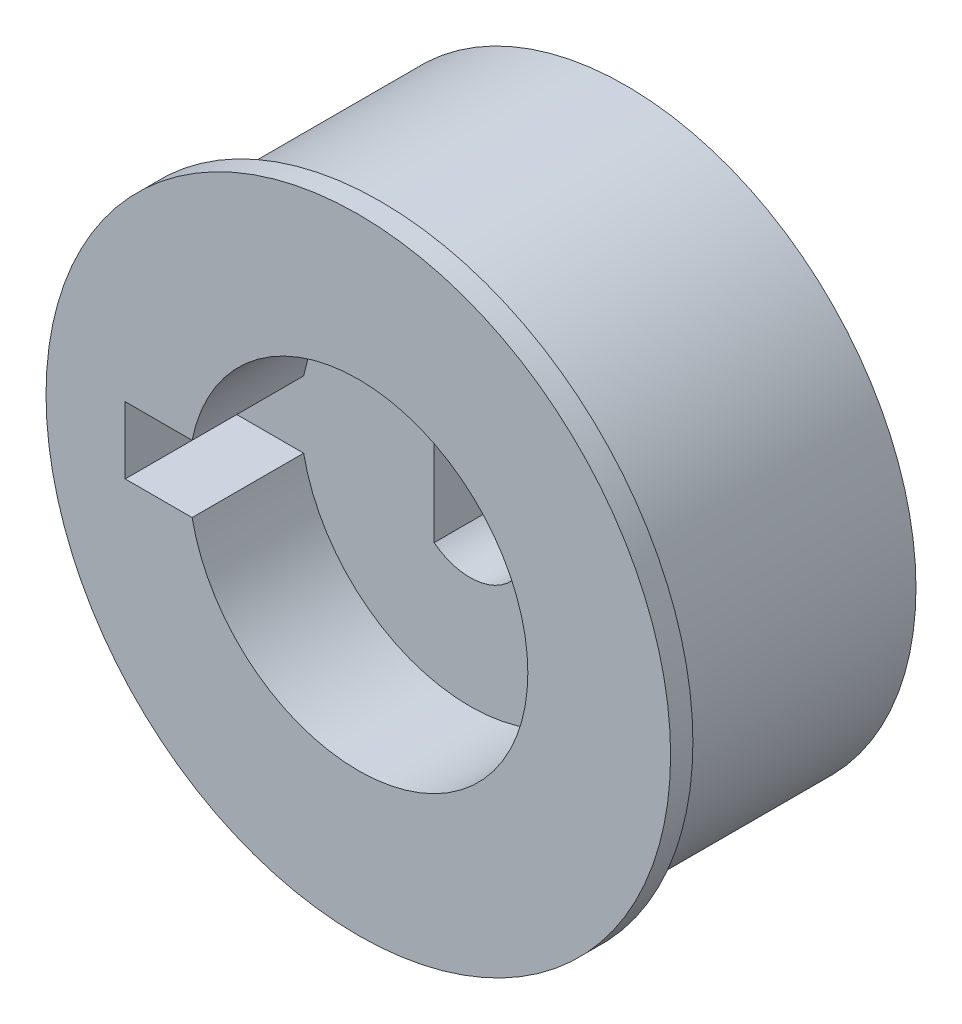
SolidWorks part; units mm, degrees
note: The reader was unsure of these and kept them because the rebuilt part matched: shared geometry of "草图1<3>", "草图1<6>".
ref_plane "前视基准面" through (0, 0, 0) normal (0, 0, 1) x (1, 0, 0)
ref_plane "上视基准面" through (0, 0, 0) normal (0, 1, 0) x (1, 0, 0)
ref_plane "右视基准面" through (0, 0, 0) normal (1, 0, 0) x (0, 0, -1)
other "Configuration Table"
sketch "草图1" plane through (0, 0, 0) normal (0, 0, 1) x (1, 0, 0)
  line L0 (-1.6, 2.0494) -> (-1.6, -2.0494)
  circle A0 centre (0, 0) radius 2.6
  circle A1 centre (0, 0) radius 13
  circle A2 centre (0, 0) radius 1.4
  circle A3 centre (0, 0) radius 14
  dimension "D1" = 5.2
  dimension "D2" = 26
  dimension "D4" = 2.8
  dimension "D5" = 28
  dimension "D3" = 1.6
extrude "凸台-拉伸1" add sketch "草图1" along normal blind 4 contours A1 A0 | L0 A0 | L0 A0 A2
extrude "凸台-拉伸2" add sketch "草图1<3>" along normal blind 12 contours A1 A0 | L0 A0
sketch "草图1<3>" plane through (0, 0, 0) normal (0, 0, 1) x (1, 0, 0) same geometry as "草图1"
extrude "凸台-拉伸3" add sketch "草图1<6>" along normal blind 1 from offset 11 contours A3 A1
sketch "草图1<6>" plane through (0, 0, 0) normal (0, 0, 1) x (1, 0, 0) same geometry as "草图1"
sketch "草图3" plane through (0, 0, 0) normal (0, 0, -1) x (-1, 0, 0)
  line L0 (3.5554, -2.9187) -> (10.8646, -7.1387)
  line L1 (0.75, 4.5384) -> (-0.75, 4.5384)
  line L2 (0.75, 4.5384) -> (0.75, 12.9783)
  line L3 (0.75, 12.9783) -> (-0.75, 12.9783)
  line L4 (-0.75, 4.5384) -> (-0.75, 12.9783)
  line L5 (3.5554, -2.9187) -> (4.3054, -1.6197)
  line L6 (4.3054, -1.6197) -> (11.6146, -5.8397)
  line L7 (10.8646, -7.1387) -> (11.6146, -5.8397)
  line L8 (-4.3054, -1.6197) -> (-11.6146, -5.8397)
  line L9 (-4.3054, -1.6197) -> (-3.5554, -2.9187)
  line L10 (-3.5554, -2.9187) -> (-10.8646, -7.1387)
  line L11 (-11.6146, -5.8397) -> (-10.8646, -7.1387)
  circle A0 centre (0, 0) radius 1.4 construction
  circle A1 centre (0, 0) radius 1.4
  circle A2 centre (0, 0) radius 13 construction
  circle A3 centre (0, 0) radius 13
  circle A4 centre (0, 0) radius 4.6
  circle A5 centre (0, 0) radius 12
  arc A6 (1.6, 2.0494) -> (1.6, -2.0494) centre (0, 0) ccw construction
  arc A7 (1.6, 2.0494) -> (1.6, -2.0494) centre (0, 0) ccw
  point P33 (0, 0)
  dimension "D1" = 2
  dimension "D3" = 1
  dimension "D2" = 1.5
  dimension "D4" = 3
extrude "切除-拉伸1" cut sketch "草图3" against normal offset from surface (5 mm away) 7 contours L4 A5 L8 A4 | L10 A5 L0 A4 | L6 A5 L2 A4 up to face at (0.5, 0, 12)
sketch "草图5" plane through (0, 0, 0) normal (0, 0, -1) x (-1, 0, 0)
  circle A0 centre (0, 0) radius 5
  dimension "D1" = 10
sketch "草图6" plane through (0, 0, 12) normal (0, 0, 1) x (1, 0, 0)
  line L0 (0, 0) -> (0, 11.2036) construction
  line L1 (-7.4505, -1.5) -> (-7.4505, 1.5)
  line L2 (-7.4505, -1.5) -> (-10.4505, -1.5)
  line L3 (-10.4505, -1.5) -> (-10.4505, 1.5)
  line L4 (-7.4505, 1.5) -> (-10.4505, 1.5)
  circle A0 centre (0, 0) radius 7.6
  arc M7 (-1.6, 2.0494) -> (-1.6, -2.0494) centre (0, 0) cw
  line M8 (-1.6, -2.0494) -> (-1.6, 2.0494)
  dimension "D1" = 15.2
  dimension "D2" = 3
  dimension "D3" = 3
extrude "切除-拉伸5" cut sketch "草图6" against normal blind 5 contours A0 L4 L3 L2 | A0 L0 L1 M7 M8 | L0 A0 M7 | L1 A0
extrude "切除-拉伸6" cut sketch "草图5" against normal offset from surface (2 mm away) 2 up to face at (0.5, 0, 4)
fillet "圆角1" radius 12 3 edges at (0, 5, 0) (-4.3301, -2.5, 0) (4.3301, -2.5, 0)
